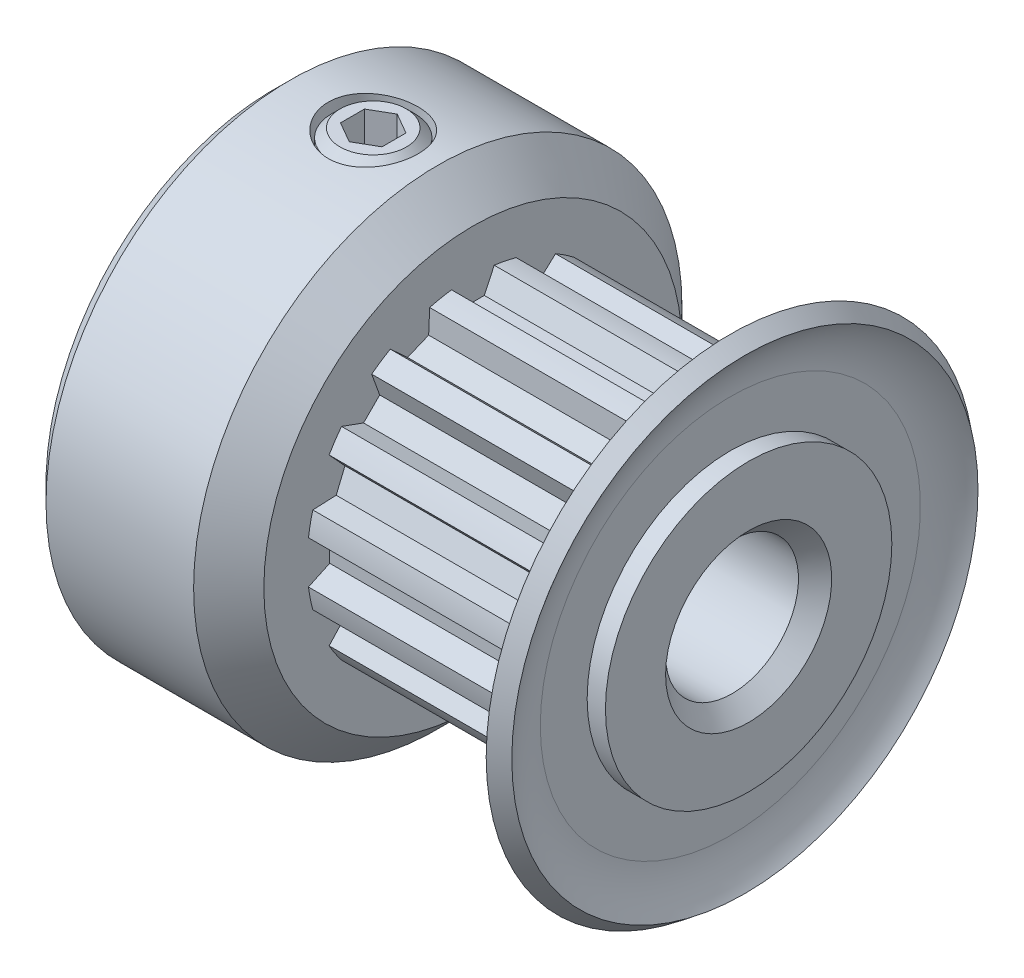
SolidWorks part; units mm, degrees
ref_plane "Front Plane" through (0, 0, 0) normal (0, 0, 1) x (1, 0, 0)
ref_plane "Top Plane" through (0, 0, 0) normal (0, 1, 0) x (1, 0, 0)
ref_plane "Right Plane" through (0, 0, 0) normal (1, 0, 0) x (0, 0, -1)
sketch "Sketch2" plane through (0, 0, 0) normal (1, 0, 0) x (0, 0, -1)
  line L3 (0, 0) -> (0, 4.3245) construction
  line L6 (0, -4.8325) -> (0, -5.15) construction
  line L7 (-0.5715, 4.7986) -> (-0.344, 4.3108)
  line L8 (0.5715, 4.7986) -> (0.344, 4.3108)
  line L9 (-0.5715, 4.7986) -> (-0.642, 4.9498)
  line L10 (0.5715, 4.7986) -> (0.642, 4.9498)
  line L12 (-0.344, 4.3108) -> (0.344, 4.3108)
  line L14 (0, 4.8325) -> (0, 5.15) construction
  line L15 (0, 0) -> (0, -1.143) construction
  circle A0 centre (0, 0) radius 5.15 construction
  circle A1 centre (0, 0) radius 4.3245 construction
  circle A2 centre (0, 0) radius 4.8325 construction
  arc A7 (0.642, 4.9498) -> (-0.642, 4.9498) centre (0, 0) ccw
  point P5 (0, 4.9912)
  dimension "D3" = 0.3175
  dimension "D1" = 50
sketch "Sketch1" plane through (0, 0, 0) normal (0, 0, 1) x (1, 0, 0)
  line L0 (-7.15, 0) -> (7.15, 0) construction
  line L1 (-7.15, 2) -> (7.15, 2)
  line L2 (-7.15, 2) -> (-7.15, 7.35)
  line L3 (-7.15, 7.35) -> (-2.207, 7.35)
  line L4 (-2.207, 7.35) -> (-1.15, 6.293)
  line L5 (-1.15, 6.293) -> (-1.15, 5.15)
  line L6 (-1.15, 5.15) -> (6.05, 5.15)
  line L7 (6.05, 5.15) -> (6.05, 5.7215)
  line L8 (6.05, 5.15) -> (7.15, 5.15) construction
  line L9 (6.6, 7.35) -> (7.15, 7.35)
  line L10 (7.15, 7.35) -> (7.15, 2)
  line L11 (6.6, 5.15) -> (6.6, 7.35) construction
  line L12 (-4.6785, 7.35) -> (-4.6785, 2) construction
  arc A0 (6.05, 5.7215) -> (6.6, 7.35) centre (8.7359, 5.7215) cw
  dimension "Bore Size" = 4
  dimension "Overall Width" = 14.3
  dimension "Inside Width" = 7.2
  dimension "Outside Width" = 8.3
  dimension "Hub Dia" = 14.7
  dimension "OD" = 14.7
  dimension "D1" = 45
  dimension "D2" = 10.3
  dimension "D3" = 1.143
  dimension "D4" = 0.5715
revolve "Revolve1" add sketch "Sketch1" angle 360 mid plane about L0
sketch "Sketch4" plane through (-1.15, 0, 0) normal (1, 0, 0) x (0, 0, -1)
  circle A0 centre (0, 0) radius 4.9912
  circle A1 centre (0, 0) radius 5.15 construction
  circle A2 centre (0, 0) radius 5.15
extrude "Cut-Extrude2" cut sketch "Sketch4" along normal up to surface (7.2 mm away) up to face at (6.05, 0, 5.15)
sketch "Sketch3" plane through (-1.15, 0, 0) normal (1, 0, 0) x (0, 0, -1)
  line L2 (-0.5715, 4.7986) -> (-0.344, 4.3108) construction
  line L3 (-0.344, 4.3108) -> (0.344, 4.3108) construction
  line L4 (0.5715, 4.7986) -> (0.344, 4.3108) construction
  line L5 (-0.642, 4.9498) -> (-0.344, 4.3108)
  line L6 (-0.344, 4.3108) -> (0.344, 4.3108)
  line L7 (0.642, 4.9498) -> (0.344, 4.3108)
  arc A1 (0.642, 4.9498) -> (-0.642, 4.9498) centre (0, 0) ccw construction
  arc A2 (0.642, 4.9498) -> (-0.642, 4.9498) centre (0, 0) ccw
extrude "Cut-Extrude1" cut sketch "Sketch3" along normal up to surface (7.2 mm away) up to face at (6.05, 0, 5.7215)
pattern_circular "CirPattern1" count 16 over 360 of "Cut-Extrude1"
sketch "Sketch5" plane through (0, 0, 0) normal (0, 1, 0) x (1, 0, 0)
  line L0 (-7.15, 7.35) -> (-7.15, -7.35) construction
  line L1 (6.05, 5.7215) -> (6.05, -5.7215) construction
  line L2 (7.15, 7.35) -> (7.15, -7.35) construction
  line L3 (-1.15, 6.293) -> (-1.15, -6.293) construction
  line L4 (6.05, 5.7215) -> (6.05, -5.7215) construction
  line L5 (-7.15, 0) -> (7.15, 0) construction
  line L6 (-7.15, 0) -> (7.15, 0) construction
  point P0 (6.05, 0)
  point P14 (6.05, 0)
  point P15 (-1.15, 0)
  dimension "D1" = 14.7
  dimension "D2" = 14.7
sketch "Sketch6" plane through (0, 0, 0) normal (0, 1, 0) x (1, 0, 0)
  line L0 (-7.15, 0) -> (-5.4, 0) construction
  line L1 (-7.15, 7.35) -> (-7.15, -7.35) construction
  line L2 (-1.15, 0) -> (-2.9, 0) construction
  line L3 (-1.15, -0.344) -> (-1.15, 0.344) construction
  line L4 (-5.4, 0) -> (-4.15, 0) construction
  line L5 (-4.15, 0) -> (-5.0339, -0.8839) construction
  circle A0 centre (-4.15, 0) radius 1.25 construction
  circle A1 centre (-4.15, 0) radius 1.35
  point P13 (-5.0339, -0.8839)
  dimension "D1" = 0.1
  dimension "D2" = 45
  dimension "SS Dia" = 2.5
extrude "Cut-Extrude3" cut sketch "Sketch6" along normal through all
sketch "Sketch7" plane through (0, 0, 0) normal (0, 0, 1) x (1, 0, 0)
  line L0 (-5.146, 7.35) -> (-4.15, 7.35)
  line L1 (-5.4, 7.096) -> (-5.4, 2.635)
  line L2 (-5.4, 2.635) -> (-5.146, 2.381)
  line L3 (-5.146, 2.381) -> (-4.15, 2.381)
  line L4 (-4.15, 2.381) -> (-4.15, 7.35) construction
  line L6 (-5.4, 7.096) -> (-5.146, 7.35)
  line L7 (-7.15, 7.35) -> (-2.207, 7.35) construction
  line L8 (-4.15, 7.35) -> (-4.15, 2.381)
  point P0 (-5.4, 7.35)
  point P4 (-5.4, 2.381)
  dimension "D2" = 0.381
revolve "Revolve2" add sketch "Sketch7" angle 360 mid plane about L4
sketch "Sketch8" plane through (0, 7.35, 0) normal (0, 1, 0) x (1, 0, 0)
  line L0 (-4.15, 0) -> (-5.4, 0) construction
  line L1 (-4.15, 0.7217) -> (-4.775, 0.3608)
  line L2 (-4.775, 0.3608) -> (-4.775, -0.3608)
  line L3 (-4.775, -0.3608) -> (-4.15, -0.7217)
  line L4 (-4.15, -0.7217) -> (-3.525, -0.3608)
  line L5 (-3.525, -0.3608) -> (-3.525, 0.3608)
  line L6 (-3.525, 0.3608) -> (-4.15, 0.7217)
  circle A0 centre (-4.15, 0) radius 0.625 construction
  point P13 (-4.775, 0)
extrude "Cut-Extrude4" cut sketch "Sketch8" against normal blind 1.016
pattern_circular "CirPattern2" [suppressed] count 2 over 90 reverse direction yes of bodies 105
pattern_circular "CirPattern3" [suppressed] count 2 over 90 reverse direction yes of bodies 107
chamfer "Chamfer1" distance 0.5 angle 45 3 edges at (-7.15, 0, 7.35) (-7.15, 0, 2) (7.15, 0, 2)
sketch "Sketch9" plane through (0, 0, 0) normal (0, 0, 1) x (1, 0, 0)
  line L0 (7.15, 4.3108) -> (7.15, 7.35)
  line L1 (7.15, 7.35) -> (7.15, 2) construction
  line L2 (6.6, 5.15) -> (6.6, 7.35) construction
  line L3 (6.6, 5.7215) -> (6.6, 4.3108)
  line L4 (6.6, 7.35) -> (6.8022, 7.6152)
  line L5 (6.6, 4.3108) -> (7.15, 4.3108)
  line L6 (6.6, 7.35) -> (7.0374, 7.0165)
  line L7 (6.8022, 7.6152) -> (7.15, 7.35)
  line L8 (-1.15, 4.3108) -> (7.15, 4.3108) construction
  line L9 (-7.15, 0) -> (7.15, 0) construction
  line L10 (-7.15, 0) -> (7.15, 0) construction
  arc A0 (6.6, 7.35) -> (6.05, 5.7215) centre (8.7359, 5.7215) ccw construction
  arc A3 (6.6, 5.7215) -> (7.0374, 7.0165) centre (8.7359, 5.7215) cw
revolve "Cut-Revolve1" cut sketch "Sketch9" angle 360 about L0
equation "\"D3@Sketch2\" = (\"hs@Sketch2\"-\"ht@Sketch2\")/2"
equation "\"D2@Sketch1\" = \"PD@Sketch2\""
equation "\"D3@Sketch1\" = \"hs@Sketch2\""
equation "\"D4@Sketch1\" = \"D3@Sketch1\"/2"
equation "\"D1@Sketch5\"=\"Hub Dia@Sketch1\""
equation "\"D2@Sketch5\"=\"OD@Sketch1\""
